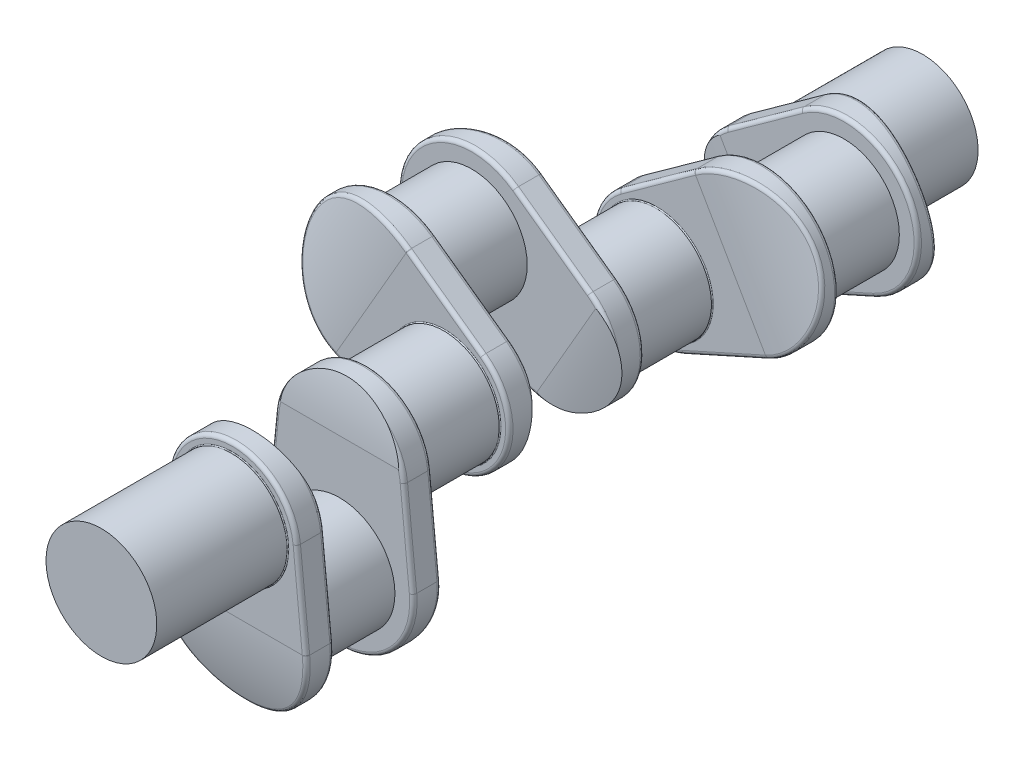
SolidWorks part; units mm, degrees
material "Ductile Iron (SN)"
ref_plane "Front Plane" through (0, 0, 0) normal (0, 0, 1) x (1, 0, 0)
ref_plane "Top Plane" through (0, 0, 0) normal (0, 1, 0) x (1, 0, 0)
ref_plane "Right Plane" through (0, 0, 0) normal (1, 0, 0) x (0, 0, -1)
sketch "Sketch1" plane through (0, 0, 0) normal (0, 0, 1) x (1, 0, 0)
  circle A0 centre (0, 0) radius 38.1
  dimension "D1" = 76.2
extrude "Boss-Extrude1" add sketch "Sketch1" along normal blind 27.31
sketch "Sketch2" plane through (0, 0, 27.31) normal (0, 0, 1) x (1, 0, 0)
  line L0 (-44.2272, 67.945) -> (-50.5454, 5.08)
  line L1 (44.2272, 67.945) -> (50.5454, 5.08)
  arc A0 (-50.5454, 5.08) -> (50.5454, 5.08) centre (0, 0) ccw
  arc A1 (44.2272, 67.945) -> (-44.2272, 67.945) centre (0, 63.5) ccw
  circle A3 centre (0, 0) radius 38.1 construction
  point P9 (0, -38.1)
  point P11 (0, -50.8)
  dimension "D1" = 88.9
  dimension "D3" = 12.7
  dimension "D2" = 63.5
extrude "Boss-Extrude2" add sketch "Sketch2" along normal blind 19
sketch "Sketch3" plane through (0, 0, 46.31) normal (0, 0, 1) x (1, 0, 0)
  circle A0 centre (0, 63.5) radius 38.1
  dimension "D1" = 76.2
extrude "Boss-Extrude3" add sketch "Sketch3" along normal blind 26.67
sketch "Sketch4" plane through (0, 0, 0) normal (1, 0, 0) x (0, 0, -1)
  line L0 (-46.31, -50.8) -> (-27.31, -50.8) construction
  line L1 (-27.31, 107.95) -> (-46.31, 107.95) construction
  line L2 (-27.31, 67.945) -> (-27.31, 107.95) construction
  line L3 (-36.81, -50.8) -> (-71.8078, -50.8)
  line L4 (-71.8078, -50.8) -> (-71.8078, 5.08)
  line L5 (-71.8078, 5.08) -> (-46.31, 5.08)
  line L6 (-32.31, 107.95) -> (-19.74, 107.95)
  line L7 (-19.74, 107.95) -> (-19.74, 74.9779)
  line L8 (-19.74, 74.9779) -> (-27.31, 74.9779)
  arc A0 (-46.31, 5.08) -> (-36.81, -50.8) centre (122.69, 5.0637) ccw
  arc A1 (-32.31, 107.95) -> (-27.31, 74.9779) centre (-196.0844, 66.2495) cw
  dimension "D1" = 169
  dimension "D3" = 169
  dimension "D2" = 5
extrude "Cut-Extrude1" cut sketch "Sketch4" against normal through all both and the other way through all
mirror "Mirror1" about plane through (0, 0, 0) normal (0, 0, 1) of bodies 104
ref_axis "Axis1" through (0, 63.5, 537.6195) along (0, 0, -1)
fillet "Fillet1" radius 2.54 22 edges at (-47.3863, 36.5125, -46.31) (0, 107.95, -46.31) (-43.7265, 71.4873, -27.31) (-47.3863, 36.5125, -27.31) (0, -50.8, -27.31) (43.7265, 71.4873, -27.31) (-43.7265, 71.4873, 27.31) (-47.3863, 36.5125, 27.31) (0, -50.8, 27.31) (43.7265, 71.4873, 27.31) (-47.3863, 36.5125, 46.31) (0, 107.95, 46.31) (47.3863, 36.5125, -46.31) (47.3863, 36.5125, -27.31) (47.3863, 36.5125, 27.31) (47.3863, 36.5125, 46.31) (50.5462, 5.0718, -46.31) (0.2541, -50.7994, -36.8102) (-50.5462, 5.0718, -46.31) (50.5462, 5.0718, 46.31) (0.2541, -50.7994, 36.8102) (-50.5462, 5.0718, 46.31)
fillet "Fillet2" radius 0.64 2 edges at (38.1, 63.5, -46.31) (38.1, 63.5, 46.31)
pattern_linear "LPattern2" count 3 spacing 145.96 along (0, 0, -1) of bodies 105
move or copy body "Body-Move/Copy1" bodies to move or copy 108 copy no rotation origin (0, 63.5, 0) rotation axis (0, 0, -1) rotation angle 120
move or copy body "Body-Move/Copy2" bodies to move or copy 109 copy no rotation origin (0, 63.5, 0) rotation axis (0, 0, 1) rotation angle 120
combine bodies "Combine1" operation type add bodies to combine 110 105 111
sketch "Sketch5" plane through (0, 0, -364.9) normal (0, 0, -1) x (-1, 0, 0)
  circle A1 centre (0, 63.5) radius 38.1
  circle A2 centre (0, 63.5) radius 38.1
  dimension "D1" = 0
extrude "Boss-Extrude4" add sketch "Sketch5" along normal blind 63.5
sketch "Sketch6" plane through (0, 0, 72.98) normal (0, 0, 1) x (1, 0, 0)
  circle A1 centre (0, 63.5) radius 38.1
  circle A2 centre (0, 63.5) radius 38.1
  dimension "D1" = 0
extrude "Boss-Extrude5" add sketch "Sketch6" along normal blind 63.5
